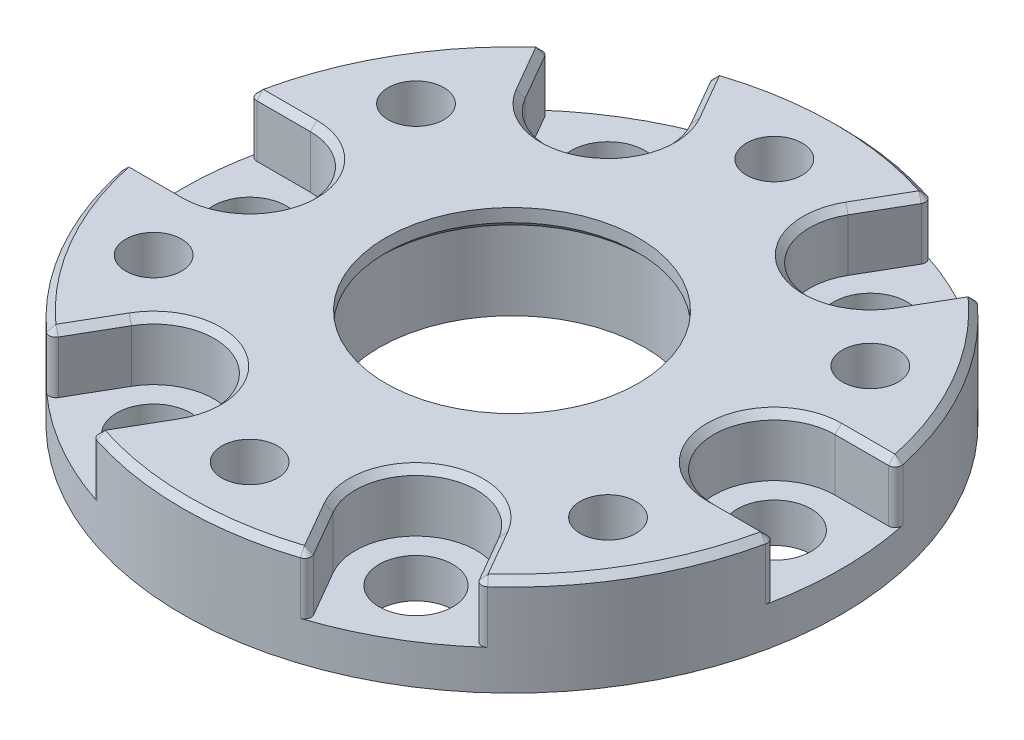
SolidWorks part; units mm, degrees
material "ABS"
ref_plane "Front Plane" through (0, 0, 0) normal (0, 0, 1) x (1, 0, 0)
ref_plane "Top Plane" through (0, 0, 0) normal (0, 1, 0) x (1, 0, 0)
ref_plane "Right Plane" through (0, 0, 0) normal (1, 0, 0) x (0, 0, -1)
sketch "Sketch1" plane through (0, 0, 0) normal (0, 0, 1) x (1, 0, 0)
  line L0 (0, 16.4693) -> (0, -1.5326) construction
  line L1 (8.1, 0) -> (20.1, 0)
  line L3 (7.7, 6) -> (20.1, 6)
  line L4 (20.1, 0) -> (20.1, 6)
  line L5 (8.1, 0) -> (8.1, 4.8)
  line L6 (8.1, 4.8) -> (7.7, 5.2)
  line L7 (7.7, 5.2) -> (7.7, 6)
  point P10 (0, 0)
  point P11 (7.9455, 6)
  point P12 (0, 0)
  dimension "D2" = 6
  dimension "D1" = 20.1
  dimension "D3" = 8.1
  dimension "D4" = 4.8
  dimension "D5" = 0.4
  dimension "D6" = 45
revolve "Revolve1" add sketch "Sketch1" angle 360 about L0
sketch "Sketch2" plane through (0, 6, 0) normal (0, 1, 0) x (1, 0, 0)
  line L0 (16, 3.7) -> (19.7565, 3.7)
  line L1 (16, -3.7) -> (19.7565, -3.7)
  line L2 (0, 0) -> (16, 0) construction
  arc A0 (16, 3.7) -> (16, -3.7) centre (16, 0) ccw
  arc A1 (19.7565, 3.7) -> (19.7565, -3.7) centre (0, 0) cw
  circle A2 centre (0, 0) radius 20.1 construction
  dimension "D2" = 3.7
  dimension "D1" = 16
extrude "Cut-Extrude1" cut sketch "Sketch2" against normal offset from surface (3.6 mm away) 2.4 up to face at (-20.1, 0, 0)
hole_wizard "M4 Clearance Hole1" positions "Sketch3" profile "Sketch5" hole size "M4" standard "ISO" end condition through all
sketch "Sketch3" plane through (0, 2.4, 0) normal (0, 1, 0) x (1, 0, 0)
  point P0 (16, 0)
sketch "Sketch5" plane through (16, 2.4, 0) normal (1, 0, 0) x (0, 0, 1)
  line L0 (0, 0) -> (0, 2.4)
  line L1 (0, 2.4) -> (2.25, 2.4)
  line L2 (2.25, 2.4) -> (2.25, 0)
  line L5 (2.25, 0) -> (0, 0)
  line L11 (0, -6.35) -> (0, 107.95) construction
  dimension "Thru Hole Dia." = 4.5
  dimension "Thru Hole Depth" = 2.4
sketch "Sketch8" plane through (0, 0, 0) normal (0, -1, 0) x (1, 0, 0)
  line L0 (0, 0) -> (0, -16) construction
  line L1 (3.2332, -16) -> (1.6166, -13.2)
  line L2 (1.6166, -13.2) -> (-1.6166, -13.2)
  line L3 (-1.6166, -13.2) -> (-3.2332, -16)
  line L4 (-3.2332, -16) -> (-1.6166, -18.8)
  line L5 (-1.6166, -18.8) -> (1.6166, -18.8)
  line L6 (1.6166, -18.8) -> (3.2332, -16)
  circle A0 centre (0, -16) radius 2.8 construction
  point P9 (0, 0)
  point P12 (3.2138, -16.3535)
  point P13 (1.5269, -18.7473)
  dimension "D1" = 5.6
  dimension "D2" = 16
extrude "Cut-Extrude2" cut sketch "Sketch8" against normal blind 2.6
hole_wizard "M3 Clearance Hole2" positions "Sketch9" profile "Sketch10" hole size "M3" standard "ISO" end condition through all
sketch "Sketch9" plane through (0, 2.6, 0) normal (0, -1, 0) x (-1, 0, 0)
  point P0 (0, 16)
sketch "Sketch10" plane through (0, 2.6, -16) normal (1, 0, 0) x (0, 0, -1)
  line L0 (0, 0) -> (0, 3.4)
  line L1 (0, 3.4) -> (1.7, 3.4)
  line L2 (1.7, 3.4) -> (1.7, 0)
  line L5 (1.7, 0) -> (0, 0)
  line L11 (0, -6.35) -> (0, 107.95) construction
  dimension "Thru Hole Dia." = 3.4
  dimension "Thru Hole Depth" = 3.4
fillet "Fillet1" radius 0.4 2 edges at (19.7565, 4.2, -3.7) (19.7565, 4.2, 3.7)
chamfer "Chamfer1" distance 1 angle 45 1 edges at (0, 2.6, -17.7)
pattern_circular "CirPattern1" count 6 over 360 about axis through (0, 16.4693, 0) along (0, 1, 0) of "Cut-Extrude1", "M4 Clearance Hole1", "Cut-Extrude2", "M3 Clearance Hole2", "Chamfer1", "Fillet1"
chamfer "Chamfer2" distance 0.4 angle 45 36 edges at (-12.3, 6, 0) (-17.6343, 6, -3.7) (-17.6343, 6, 3.7) (-19.5795, 6, -3.8483) (-19.5795, 6, 3.8483) (-17.4071, 6, -10.05) (-17.4071, 6, 10.05) (-13.1225, 6, -15.0322) (-13.1225, 6, 15.0322) (-12.0215, 6, -13.4218) (-12.0215, 6, 13.4218) (-6.15, 6, -10.6521) (-6.15, 6, 10.6521) (-5.6129, 6, -17.1218) (-5.6129, 6, 17.1218) (-6.457, 6, -18.8805) (-6.457, 6, 18.8805) (0, 6, -20.1) (0, 6, 20.1) (6.457, 6, -18.8805) (6.457, 6, 18.8805) (5.6129, 6, -17.1218) (5.6129, 6, 17.1218) (6.15, 6, -10.6521) (6.15, 6, 10.6521) (12.0215, 6, -13.4218) (12.0215, 6, 13.4218) (13.1225, 6, -15.0322) (13.1225, 6, 15.0322) (17.4071, 6, -10.05) (17.4071, 6, 10.05) (19.5795, 6, -3.8483) (19.5795, 6, 3.8483) (17.6343, 6, -3.7) (17.6343, 6, 3.7) (12.3, 6, 0)
equation "\"PinCenterDiameter\"= 50mm"
equation "\"HousingDiameter\"= 60mm"
equation "\"LooseOneSidedClearance\"= 0.2mm"
equation "\"TightOneSidedClearance\"= 0.2mm"
equation "\"LowerLinkLength\"= 150mm"
equation "\"M3HexWidthFlat\"= 5.6mm"
equation "\"LowerBearingBore\"= 40mm"
equation "\"LowerBearingDepth\"= 6mm"
equation "\"D2@Sketch1\"=\"LowerBearingDepth\""
equation "\"D1@Sketch1\"=20.1mm"
